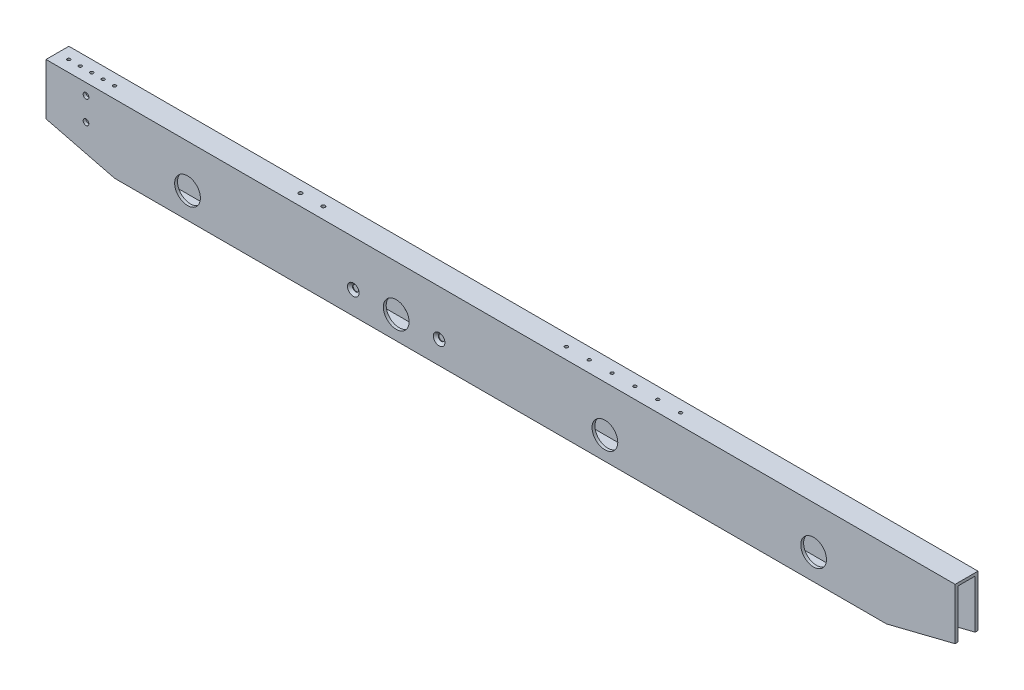
SolidWorks part; units mm, degrees
material "6061-T6 (SS)"
ref_plane "Front Plane" through (0, 0, 0) normal (0, 0, 1) x (1, 0, 0)
ref_plane "Top Plane" through (0, 0, 0) normal (0, 1, 0) x (1, 0, 0)
ref_plane "Right Plane" through (0, 0, 0) normal (1, 0, 0) x (0, 0, -1)
sketch "Sketch1" plane through (0, 0, 0) normal (0, 0, 1) x (1, 0, 0)
  line L0 (0, -12.7) -> (-347.6625, -9.525) construction
  line L1 (-504.825, 38.1) -> (504.825, 38.1)
  line L2 (-504.825, 38.1) -> (-504.825, -38.1)
  line L3 (-504.825, -38.1) -> (504.825, -38.1)
  line L4 (504.825, 38.1) -> (504.825, -38.1)
  line L5 (-504.825, 38.1) -> (504.825, -38.1) construction
  line L6 (-504.825, -38.1) -> (504.825, 38.1) construction
  line L7 (-504.825, -38.1) -> (504.825, -38.1) construction
  line L8 (-504.825, -38.1) -> (-504.825, -12.7) construction
  line L9 (-327.025, -63.5) -> (327.025, -63.5) construction
  line L10 (-504.825, -12.7) -> (504.825, -12.7) construction
  line L11 (504.825, -38.1) -> (504.825, -12.7) construction
  line L12 (0, -12.7) -> (347.6625, -9.525) construction
  line L13 (-115.8875, -12.7) -> (115.8875, -12.7) construction
  circle A0 centre (115.8875, -12.7) radius 14.2875
  circle A1 centre (-347.6625, -9.525) radius 14.2875
  circle A2 centre (347.6625, -9.525) radius 14.2875
  circle A3 centre (-115.8875, -12.7) radius 14.2875
  point P0 (0, 0)
  dimension "D5" = 28.575
  dimension "D4" = 28.575
  dimension "D8" = 231.775
  dimension "D6" = 231.775
  dimension "D7" = 231.775
  dimension "D1" = 76.2
  dimension "D2" = 1009.65
  dimension "D3" = 25.4
extrude "Boss-Extrude2" add sketch "Sketch1" along normal mid plane 25.4
sketch "Sketch3" plane through (504.825, 0, 0) normal (1, 0, 0) x (0, 0, -1)
  line L8 (9.525, -34.925) -> (9.525, 34.925)
  line L9 (9.525, 34.925) -> (-9.525, 34.925)
  line L10 (-9.525, 34.925) -> (-9.525, -34.925)
  line L11 (-9.525, -34.925) -> (9.525, -34.925)
  line L12 (9.525, -34.925) -> (9.525, 34.925)
  line L13 (9.525, 34.925) -> (-9.525, 34.925)
  line L14 (-9.525, 34.925) -> (-9.525, -34.925)
  line L15 (-9.525, -34.925) -> (9.525, -34.925)
  dimension "D1" = 3.175
extrude "Cut-Extrude2" cut sketch "Sketch3" against normal through all
sketch "Sketch4" plane through (0, 0, 12.7) normal (0, 0, 1) x (1, 0, 0)
  line L0 (-504.825, -38.1) -> (-504.825, -19.05)
  line L1 (-504.825, 38.1) -> (-504.825, -38.1) construction
  line L2 (-504.825, -19.05) -> (-428.625, -38.1)
  line L3 (-504.825, -38.1) -> (504.825, -38.1) construction
  line L4 (-428.625, -38.1) -> (-504.825, -38.1)
  line L5 (0, -38.1) -> (0, 38.1) construction
  line L6 (504.825, 38.1) -> (-504.825, 38.1) construction
  line L7 (428.625, -38.1) -> (504.825, -38.1)
  line L8 (504.825, -38.1) -> (504.825, -19.05)
  line L9 (504.825, -19.05) -> (428.625, -38.1)
  dimension "D1" = 19.05
  dimension "D2" = 76.2
  dimension "D3" = 57.15
extrude "Cut-Extrude3" cut sketch "Sketch4" against normal through all
sketch "Sketch9" plane through (0, 38.1, 0) normal (0, 1, 0) x (1, 0, 0)
  line L0 (-504.825, -12.7) -> (-504.825, 12.7) construction
  line L1 (0, -12.7) -> (0, 12.7) construction
  line L2 (504.825, -12.7) -> (-504.825, -12.7) construction
  line L3 (504.825, 12.7) -> (-504.825, 12.7) construction
  circle A0 centre (-492.125, 0) radius 1.7272
  circle A1 centre (-441.325, 0) radius 1.7272
  circle A2 centre (-479.425, 0) radius 1.7272
  circle A3 centre (-466.725, 0) radius 1.7272
  circle A4 centre (-454.025, 0) radius 1.7272
  point P2 (-504.825, 0)
  dimension "D1" = 3.4544
  dimension "D2" = 12.7
  dimension "D3" = 4
  dimension "D4" = 2
extrude "Cut-Extrude5" cut sketch "Sketch9" against normal blind 6.35
sketch "Sketch12" plane through (0, 38.1, 0) normal (0, 1, 0) x (1, 0, 0)
  line L0 (504.825, -12.7) -> (504.825, 12.7) construction
  circle A0 centre (187.325, 0) radius 1.7272
  circle A1 centre (161.925, 0) radius 1.7272
  circle A2 centre (136.525, 0) radius 1.7272
  circle A3 centre (111.125, 0) radius 1.7272
  circle A4 centre (85.725, 0) radius 1.7272
  circle A5 centre (60.325, 0) radius 1.7272
  point P2 (504.825, 0)
  dimension "D1" = 3.4544
  dimension "D2" = 317.5
  dimension "D3" = 6
extrude "Cut-Extrude8" cut sketch "Sketch12" against normal blind 5.08
hole_wizard "CSK for 1/4 Flat Head Machine Screw (100)1" positions "Sketch14" profile "Sketch13" countersink size "1/4" standard "ANSI Inch" end condition through all
sketch "Sketch14" plane through (0, 0, 12.7) normal (0, 0, 1) x (1, 0, 0)
  circle A1 centre (-115.8875, -12.7) radius 14.2875 construction
  point P0 (-68.2625, -12.7)
  point P2 (-163.5125, -12.7)
  dimension "D4" = 47.625
  dimension "D3" = 47.625
sketch "Sketch13" plane through (-68.2625, -12.7, 12.7) normal (1, 0, 0) x (0, -1, 0)
  line L0 (0, 0) -> (0, 25.4)
  line L1 (0, 25.4) -> (3.3782, 25.4)
  line L2 (3.3782, 25.4) -> (3.3782, 2.5682)
  line L3 (3.3782, 2.5682) -> (6.4389, 0)
  line L5 (6.4389, 0) -> (0, 0)
  line L6 (-3.3782, 2.5682) -> (-6.4389, 0) construction
  line L11 (0, -6.35) -> (0, 107.95) construction
  dimension "Thru Hole Dia." = 6.7564
  dimension "Thru Hole Depth" = 25.4
  dimension "Near C'Sink Dia." = 12.8778
  dimension "Near C'Sink Angle" = 100
sketch "Sketch15" plane through (0, -38.1, 0) normal (0, -1, 0) x (-1, 0, 0)
  line L1 (-504.825, 9.525) -> (-504.825, -9.525) construction
  circle A0 centre (396.875, 0) radius 1.7272
  circle A1 centre (320.675, 0) radius 1.7272
  circle A2 centre (244.475, 0) radius 1.7272
  circle A3 centre (168.275, 0) radius 1.7272
  circle A4 centre (92.075, 0) radius 1.7272
  circle A5 centre (15.875, 0) radius 1.7272
  circle A6 centre (-60.325, 0) radius 1.7272
  dimension "D1" = 3.4544
  dimension "D2" = 444.5
  dimension "D3" = 7
extrude "Cut-Extrude9" cut sketch "Sketch15" against normal blind 6.35
sketch "Sketch16" plane through (0, 0, -12.7) normal (0, 0, -1) x (-1, 0, 0)
  circle A0 centre (115.8875, -12.7) radius 17.4625
  dimension "D1" = 34.925
extrude "Cut-Extrude10" cut sketch "Sketch16" against normal blind 3.81
hole_wizard "1/4 (0.25) Diameter Hole1" positions "Sketch19" profile "Sketch18" hole size "1/4" standard "ANSI Inch" end condition through all
sketch "Sketch19" plane through (0, 0, 12.7) normal (0, 0, 1) x (1, 0, 0)
  line L0 (-504.825, 38.1) -> (-504.825, -19.05) construction
  line L1 (-479.425, -25.4) -> (-479.425, 3.7361) construction
  line L2 (-428.625, -38.1) -> (-504.825, -19.05) construction
  line L5 (504.825, 38.1) -> (-504.825, 38.1) construction
  point P0 (-460.375, 25.4)
  point P2 (-460.375, 0)
  dimension "D1" = 19.05
  dimension "D2" = 25.4
  dimension "D3" = 25.4
  dimension "D4" = 12.7
sketch "Sketch18" plane through (-460.375, 25.4, 12.7) normal (1, 0, 0) x (0, -1, 0)
  line L0 (0, 0) -> (0, 25.4)
  line L1 (0, 25.4) -> (3.175, 25.4)
  line L2 (3.175, 25.4) -> (3.175, 0)
  line L5 (3.175, 0) -> (0, 0)
  line L11 (0, -6.35) -> (0, 107.95) construction
  dimension "Thru Hole Dia." = 6.35
  dimension "Thru Hole Depth" = 25.4
hole_wizard "#10-32 Tapped Hole3" positions "Sketch23" profile "Sketch22" tap size "#10-32" standard "ANSI Inch" end condition through all
sketch "Sketch23" plane through (0, 38.1, 0) normal (0, 1, 0) x (1, 0, 0)
  line L0 (-504.825, -12.7) -> (-504.825, 12.7) construction
  point P0 (-234.95, 0)
  point P4 (-209.55, 0)
  dimension "D1" = 269.875
  dimension "D2" = 25.4
sketch "Sketch22" plane through (-234.95, 38.1, 0) normal (1, 0, 0) x (0, 0, 1)
  line L0 (0, 0) -> (0, 76.2)
  line L1 (0, 76.2) -> (2.0193, 76.2)
  line L2 (2.0193, 76.2) -> (2.0193, 0)
  line L5 (2.0193, 0) -> (0, 0)
  line L11 (0, -6.35) -> (0, 107.95) construction
  dimension "Thread Major Dia." = 4.0386
  dimension "Thru Tap Drill Depth" = 76.2
